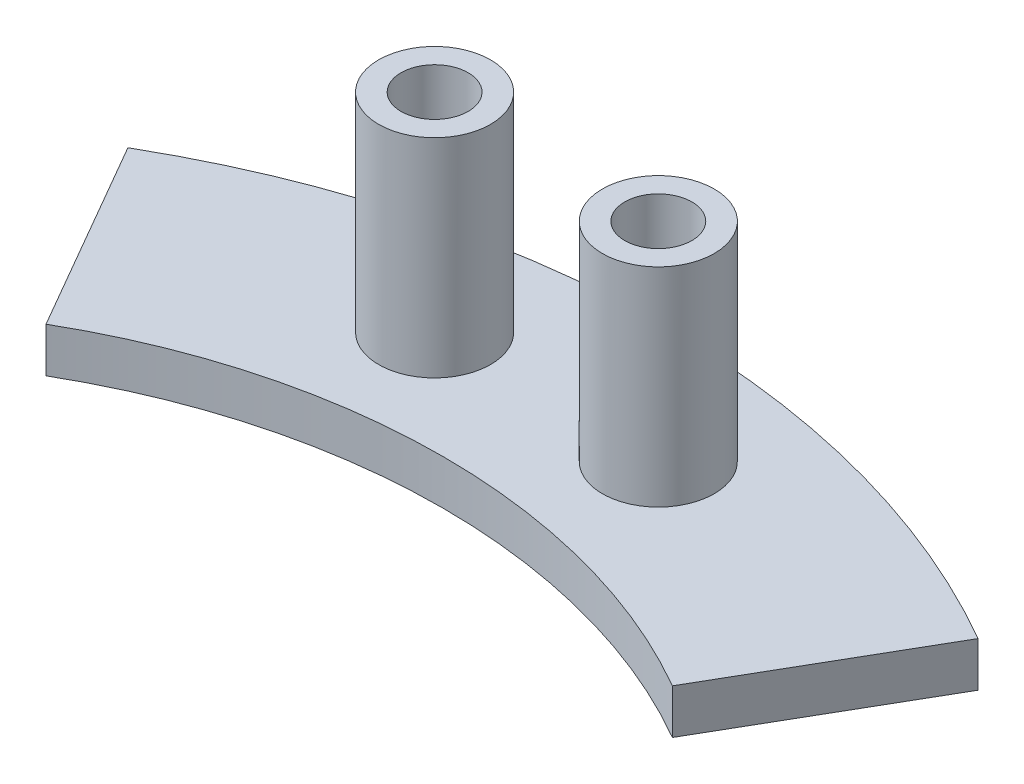
SolidWorks part; units mm, degrees
ref_plane "Front Plane" through (0, 0, 0) normal (0, 0, 1) x (1, 0, 0)
ref_plane "Top Plane" through (0, 0, 0) normal (0, 1, 0) x (1, 0, 0)
ref_plane "Right Plane" through (0, 0, 0) normal (1, 0, 0) x (0, 0, -1)
sketch "Sketch1" plane through (0, 0, 0) normal (0, 1, 0) x (1, 0, 0)
  line L0 (-14, 24.2487) -> (-19, 32.909) construction
  line L1 (14, 24.2487) -> (19, 32.909) construction
  line L2 (0, 0) -> (4, 0) construction
  line L3 (-19, 32.909) -> (-14, 24.2487)
  line L4 (19, 32.909) -> (14, 24.2487)
  circle A0 centre (0, 0) radius 28 construction
  circle A1 centre (0, 0) radius 38 construction
  arc A2 (-19, 32.909) -> (19, 32.909) centre (0, 0) cw
  arc A3 (-14, 24.2487) -> (14, 24.2487) centre (0, 0) cw
  arc A4 (-16.5, 28.5788) -> (16.5, 28.5788) centre (0, 0) cw construction
  dimension "D1" = 76
  dimension "D2" = 56
  dimension "D6" = 60
  dimension "D3" = 60
extrude "Boss-Extrude1" add sketch "Sketch1" along normal blind 2
sketch "Sketch2" plane through (0, 2, 0) normal (0, 1, 0) x (1, 0, 0)
  line L1 (14, 24.2487) -> (19, 32.909) construction
  line L2 (-5, 32.619) -> (5, 32.619) construction
  line L3 (0, 32.619) -> (0, 0) construction
  line L5 (-19, 32.909) -> (-14, 24.2487) construction
  arc A0 (-16.5, 28.5788) -> (16.5, 28.5788) centre (0, 0) cw construction
  circle A1 centre (-5, 32.619) radius 2.5
  circle A2 centre (5, 32.619) radius 2.5
  dimension "D1" = 5
  dimension "D4" = 33
  dimension "D2" = 10
  dimension "D3" = 32.619
extrude "Boss-Extrude2" add sketch "Sketch2" along normal blind 9.3
sketch "Sketch5" plane through (0, 11.3, 0) normal (0, 1, 0) x (1, 0, 0)
  circle A0 centre (-5, 32.619) radius 1.5
  circle A2 centre (5, 32.619) radius 1.5
  dimension "D1" = 3
extrude "Cut-Extrude1" cut sketch "Sketch5" against normal blind 3.5
sketch "Sketch6" plane through (0, 0, 0) normal (0, -1, 0) x (1, 0, 0)
  line L0 (0, 0) -> (0, -33) construction
  line L1 (-19, -32.909) -> (-14, -24.2487) construction
  line L2 (14, -24.2487) -> (19, -32.909) construction
  arc A0 (-16.5, -28.5788) -> (16.5, -28.5788) centre (0, 0) ccw construction
  circle A1 centre (0, -33) radius 1.5
  dimension "D1" = 3
extrude "Cut-Extrude2" cut sketch "Sketch6" against normal blind 1
